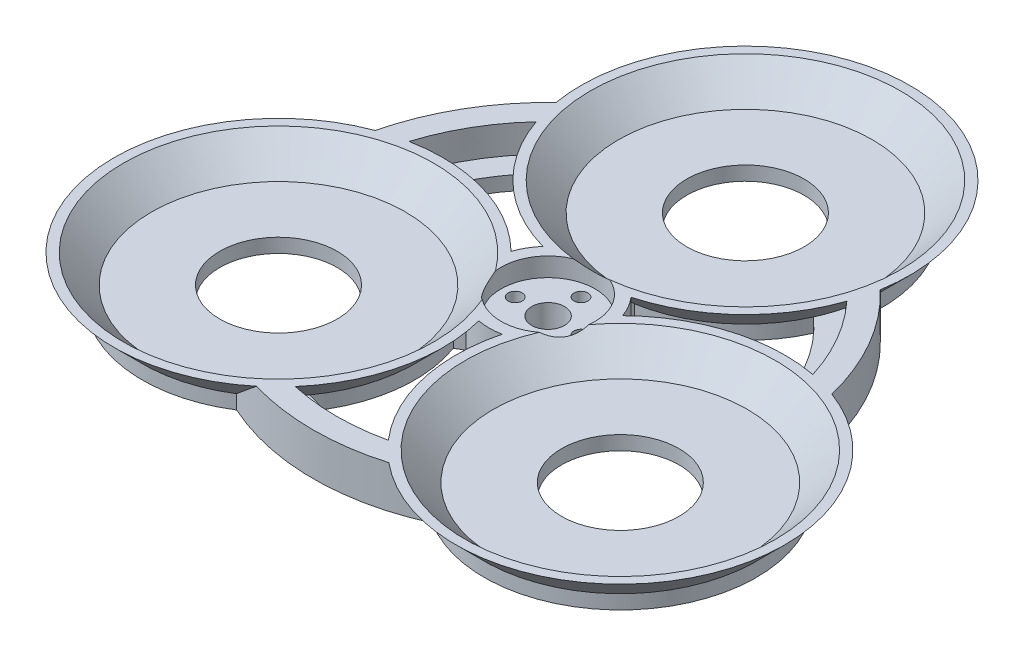
SolidWorks part; units mm, degrees
material "聚脂树脂"
ref_plane "前视基准面" through (0, 0, 0) normal (0, 0, 1) x (1, 0, 0)
ref_plane "上视基准面" through (0, 0, 0) normal (0, 1, 0) x (1, 0, 0)
ref_plane "右视基准面" through (0, 0, 0) normal (1, 0, 0) x (0, 0, -1)
other "Configuration Table"
sketch "草图1" plane through (0, 0, 0) normal (0, 1, 0) x (1, 0, 0)
  line L0 (0, 0) -> (0, 11.819) construction
  line L1 (0, 0) -> (17.9433, 0) construction
  circle A0 centre (0, 0) radius 10
  circle A1 centre (0, 7) radius 1.5
  circle A2 centre (0, 0) radius 3.5
  circle A3 centre (7, 0) radius 1.5
  circle A4 centre (0, -7) radius 1.5
  circle A5 centre (-7, 0) radius 1.5
  dimension "D1" = 7
  dimension "D2" = 20
  dimension "D3" = 3
  dimension "D4" = 3
  dimension "D5" = 7
  dimension "D6" = 7
extrude "凸台-拉伸1" add sketch "草图1" along normal blind 5
sketch "草图3" plane through (0, 0, 0) normal (0, -1, 0) x (1, 0, 0)
  circle A0 centre (0, 0) radius 10
  circle A1 centre (0, 0) radius 12.5
  dimension "D1" = 20
  dimension "D2" = 25
extrude "凸台-拉伸2" add sketch "草图3" against normal blind 9
sketch "草图4" plane through (0, 0, 0) normal (0, 1, 0) x (1, 0, 0)
  line L0 (0, 0) -> (0, 69.4265) construction
  line L1 (0, 0) -> (77.5532, 0) construction
  line L2 (0, 0) -> (-79.1106, 0) construction
  line L3 (12.4216, -1.3981) -> (14.1344, -2.387)
  line L4 (7.4216, -10.0583) -> (9.1344, -11.0473)
  line L5 (-7.4216, -10.0583) -> (-9.1344, -11.0473)
  line L6 (-12.4216, -1.3981) -> (-14.1344, -2.387)
  line L12 (-5, 11.4564) -> (-5, 13.4343)
  line L13 (5, 11.4564) -> (5, 13.4343)
  circle A0 centre (0, 0) radius 12.5
  circle A2 centre (0, 42) radius 29
  circle A5 centre (0, 7) radius 1.5 construction
  circle A8 centre (36.3731, -21) radius 29
  circle A9 centre (-36.3731, -21) radius 29
  circle A10 centre (0, 0) radius 50
  circle A11 centre (0, 0) radius 40
  point P14 (0, 0)
  point P15 (0, 0)
  point P16 (0, 0)
  point P17 (0, 0)
  point P24 (0, 0)
  point P29 (0, 0)
  point P40 (0, 0)
  point P43 (0, 0)
  point P44 (0, 0)
  point P45 (0, 0)
  point P46 (0, 0)
  circle M13 centre (0, 0) radius 12.5
  dimension "D1" = 25
  dimension "D4" = 58
  dimension "D6" = 42
  dimension "D8" = 80
  dimension "D9" = 100
  dimension "D7" = 3
  dimension "D2" = 90
  dimension "D3" = 90
  dimension "D15" = 10
  dimension "D12" = 3
  dimension "D13" = 3
  dimension "D5" = 3
extrude "凸台-拉伸3" add sketch "草图4" along normal blind 3 contours A2 A11 A10 | A2 A10 | A11 A2 | A11 A9 | A9 A11 A10 | A9 A10 | A8 A10 | A8 A11 A10 | A11 A8 | L5 A9 L6 M13 | L12 A2 L13 M13 | L3 A8 L4 M13 | A2 A11 A9 A10 | A9 A11 A8 A10 | A8 A11 A2 A10 region at (10.9217, 0, 6.3056) region at (23.3564, 0, 13.4848) region at (38.3886, 0, -22.1637) region at (36.1473, 0, 20.8697) region at (-10.9217, 0, 6.3056) region at (0, 0, -12.6113) region at (0, 0, 44.3274) region at (49.258, 0, 28.4391) region at (0, 0, -41.7393) region at (0, 0, -26.9697) region at (-23.3564, 0, 13.4848) region at (-36.1473, 0, 20.8697) region at (0, 0, -56.8782) region at (-38.3886, 0, -22.1637) region at (-49.258, 0, 28.4391)
sketch "草图15" plane through (0, 3, 0) normal (0, 1, 0) x (1, 0, 0)
  line L0 (-5, 11.4564) -> (-5, 13.4343) construction
  line L1 (5, 11.4564) -> (5, 13.4343) construction
  line L2 (7.4216, -10.0583) -> (9.1344, -11.0473) construction
  line L3 (12.4216, -1.3981) -> (14.1344, -2.387) construction
  line L4 (-7.4216, -10.0583) -> (-9.1344, -11.0473) construction
  line L5 (-12.4216, -1.3981) -> (-14.1344, -2.387) construction
  line L6 (-5, 11.4564) -> (-5, 13.4343)
  line L7 (5, 11.4564) -> (5, 13.4343)
  line L8 (7.4216, -10.0583) -> (9.1344, -11.0473)
  line L9 (12.4216, -1.3981) -> (14.1344, -2.387)
  line L10 (-7.4216, -10.0583) -> (-9.1344, -11.0473)
  line L11 (-12.4216, -1.3981) -> (-14.1344, -2.387)
  circle A0 centre (-36.3731, -21) radius 29
  circle A1 centre (36.3731, -21) radius 29
  circle A2 centre (0, 42) radius 29
  circle A3 centre (0, 0) radius 12.5 construction
  arc A4 (-12.4216, -1.3981) -> (-7.4216, -10.0583) centre (0, 0) ccw construction
  circle A5 centre (0, 0) radius 12.5
  arc A6 (-49.7771, 4.7164) -> (-20.804, -45.4664) centre (-36.3731, -21) ccw
  arc A7 (-20.804, -45.4664) -> (20.804, -45.4664) centre (0, 0) ccw
  arc A8 (20.804, -45.4664) -> (49.7771, 4.7164) centre (36.3731, -21) ccw
  arc A9 (49.7771, 4.7164) -> (28.973, 40.75) centre (0, 0) ccw
  arc A10 (28.973, 40.75) -> (-28.973, 40.75) centre (0, 42) ccw
  arc A11 (-28.973, 40.75) -> (-49.7771, 4.7164) centre (0, 0) ccw
  arc A12 (-49.7771, 4.7164) -> (-20.804, -45.4664) centre (-36.3731, -21) ccw
  arc A13 (-20.804, -45.4664) -> (20.804, -45.4664) centre (0, 0) ccw
  arc A14 (20.804, -45.4664) -> (49.7771, 4.7164) centre (36.3731, -21) ccw
  arc A15 (49.7771, 4.7164) -> (28.973, 40.75) centre (0, 0) ccw
  arc A16 (28.973, 40.75) -> (-28.973, 40.75) centre (0, 42) ccw
  arc A17 (-28.973, 40.75) -> (-49.7771, 4.7164) centre (0, 0) ccw
  arc A18 (-12.4216, -1.3981) -> (-7.4216, -10.0583) centre (0, 0) ccw
  circle A19 centre (0, 0) radius 45
  arc M9 (-20.804, -45.4664) -> (20.804, -45.4664) centre (0, 0) ccw
  arc M11 (49.7771, 4.7164) -> (28.973, 40.75) centre (0, 0) ccw
  arc M13 (-28.973, 40.75) -> (-49.7771, 4.7164) centre (0, 0) ccw
  arc M14 (-39.2202, 7.8599) -> (-26.417, 30.0357) centre (0, 0) cw
  line M16 (-5, 13.4343) -> (-5, 11.4564)
  arc M17 (-5, 11.4564) -> (5, 11.4564) centre (0, 0) cw
  line M18 (5, 11.4564) -> (5, 13.4343)
  arc M20 (26.417, 30.0357) -> (39.2202, 7.8599) centre (0, 0) cw
  line M22 (14.1344, -2.387) -> (12.4216, -1.3981)
  arc M23 (12.4216, -1.3981) -> (7.4216, -10.0583) centre (0, 0) cw
  line M24 (7.4216, -10.0583) -> (9.1344, -11.0473)
  arc M26 (12.8032, -37.8956) -> (-12.8032, -37.8956) centre (0, 0) cw
  line M28 (-9.1344, -11.0473) -> (-7.4216, -10.0583)
  arc M29 (-7.4216, -10.0583) -> (-12.4216, -1.3981) centre (0, 0) cw
  line M30 (-12.4216, -1.3981) -> (-14.1344, -2.387)
  dimension "D2" = 58
  dimension "D3" = 58
  dimension "D4" = 58
  dimension "D5" = 90
  dimension "D1" = 0
extrude "凸台-拉伸4" add sketch "草图15" along normal up to surface (6 mm away) contours A0 M28 M29 M30 | A2 M16 M17 M18 | A1 M22 M23 M24 | A1 A0 M26 M9 | A2 A0 M13 M14 | A2 A1 M20 M11 region at (0, 3, -12.6113) region at (-10.9217, 3, 6.3056) region at (-40.1308, 3, -23.1695) region at (10.9217, 3, 6.3056) region at (40.1308, 3, -23.1695) region at (0, 3, 46.339) up to face at (0, 9, -10)
sketch "草图5" plane through (0, 0, 0) normal (1, 0, 0) x (0, 0, -1)
  line L0 (0, 0) -> (0, 45.57) construction
  line L1 (42, 0) -> (42, 45.57) construction
  line L3 (69, 0) -> (69, 36.9521) construction
  line L5 (69, 3) -> (71, 3)
  line L6 (71, 3) -> (77, 9)
  line L7 (77, 9) -> (75, 9)
  line L8 (75, 9) -> (69, 3)
  dimension "D1" = 42
  dimension "D2" = 27
  dimension "D3" = 6
  dimension "D4" = 6
revolve "旋转1" add sketch "草图5" angle 360 about L1
ref_axis "基准轴1" through (0, -0.6, 0) along (0, 1, 0)
pattern_circular "阵列(圆周)1" count 3 over 360 about axis through (0, -0.6, 0) along (0, 1, 0) of "旋转1" reverse direction yes
sketch "草图9" plane through (0, 9, 0) normal (0, 1, 0) x (1, 0, 0)
  circle A0 centre (0, 0) radius 10
  dimension "D1" = 20
sketch "草图13" plane through (0, 3, 0) normal (0, 1, 0) x (1, 0, 0)
  circle A0 centre (0, 42) radius 12.5
  circle A3 centre (36.3731, -21) radius 12.5
  circle A4 centre (-36.3731, -21) radius 12.5
  point P9 (0, 0)
  dimension "D1" = 25
extrude "切除-拉伸2" cut sketch "草图13" against normal blind 10
sketch "草图16" plane through (0, 0, 0) normal (1, 0, 0) x (0, 0, -1)
  line L0 (42, 0) -> (42, 33.3265) construction
  line L1 (40.75, 0) -> (71, 0) construction
  line L2 (0, -0.6) -> (0, 12.6) construction
  line L3 (42, 3) -> (69, 3)
  line L4 (30.0357, 3) -> (13.4343, 3) construction
  line L5 (69, 3) -> (75, 9)
  line L6 (74.619, 9) -> (9, 9) construction
  line L7 (75, 9) -> (42, 9)
  line L8 (42, 9) -> (42, 3)
  line L10 (71, 3) -> (77, 9) construction
  dimension "D1" = 42
  dimension "D2" = 27
revolve "切除-旋转1" cut sketch "草图16" angle 360 about L0
pattern_circular "阵列(圆周)2" count 3 over 360 about axis through (0, -0.6, 0) along (0, 1, 0) of "切除-旋转1"
sketch "草图18" plane through (0, 9, 0) normal (0, 1, 0) x (1, 0, 0)
  circle A0 centre (0, 0) radius 10
  dimension "D1" = 20
extrude "切除-拉伸3" cut sketch "草图18" against normal blind 4
